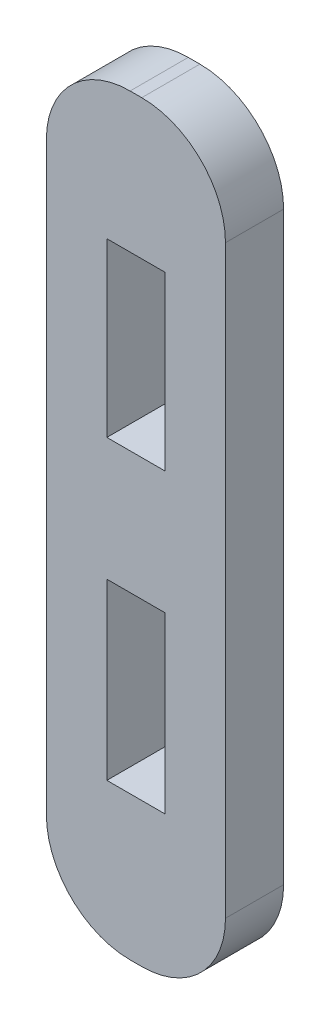
SolidWorks part; units mm, degrees
ref_plane "Front Plane" through (0, 0, 0) normal (0, 0, 1) x (1, 0, 0)
ref_plane "Top Plane" through (0, 0, 0) normal (0, 1, 0) x (1, 0, 0)
ref_plane "Right Plane" through (0, 0, 0) normal (1, 0, 0) x (0, 0, -1)
sketch "Sketch1" plane through (0, 0, 0) normal (0, 0, 1) x (1, 0, 0)
  line L0 (3.2385, 18.8942) -> (1.651, 18.8942) construction
  line L1 (0, 0) -> (4.8895, 0)
  line L2 (0, 0) -> (0, 20.5452)
  line L3 (0, 20.5452) -> (4.8895, 20.5452)
  line L4 (4.8895, 0) -> (4.8895, 20.5452)
  line L7 (3.2385, 16.7352) -> (3.2385, 18.8942) construction
  dimension "D1" = 1.651
  dimension "D2" = 1.651
extrude "Boss-Extrude1" add sketch "Sketch1" along normal blind 1.5875
sketch "Sketch2" plane through (0, 0, 0) normal (0, 0, -1) x (-1, 0, 0)
  line L1 (-3.2385, 14.1952) -> (-3.2385, 12.0362)
  line L2 (-3.2385, 12.0362) -> (-1.651, 12.0362)
  line L3 (-1.651, 12.0362) -> (-1.651, 14.1952)
  line L4 (-1.651, 15.6786) -> (-1.651, 18.5626) construction
  line L6 (-1.651, 16.7352) -> (-1.651, 18.8942) construction
  line L7 (-3.2385, 15.6786) -> (-3.2385, 18.5626) construction
  line L8 (-1.651, 5.2233) -> (-1.651, 6.4075) construction
  line L9 (-3.2385, 5.2233) -> (-3.2385, 4.8666) construction
  line L10 (-3.2385, 16.7352) -> (-1.651, 16.7352) construction
  line L11 (-3.2385, 6.4075) -> (-3.2385, 5.2233) construction
  line L12 (-1.651, 4.8666) -> (-1.651, 5.2233) construction
  line L13 (-1.651, 5.2233) -> (-1.651, 6.4075)
  line L14 (-1.651, 15.3513) -> (-1.651, 15.6786) construction
  line L15 (-1.651, 14.1952) -> (-1.651, 15.3513) construction
  line L16 (-3.2385, 16.7352) -> (-1.651, 16.7352)
  line L17 (-3.2385, 15.6786) -> (-3.2385, 15.3513) construction
  line L18 (-3.2385, 15.3513) -> (-3.2385, 14.1952) construction
  line L19 (-1.651, 15.6786) -> (-1.651, 16.7352)
  line L20 (-3.2385, 5.2233) -> (-3.2385, 4.8666)
  line L21 (-3.2385, 6.4075) -> (-3.2385, 5.2233)
  line L22 (-3.2385, 3.9278) -> (-1.651, 3.9278) construction
  line L25 (-3.2385, 15.6786) -> (-3.2385, 16.7352)
  line L26 (-1.651, 15.3513) -> (-1.651, 15.6786)
  line L27 (-1.651, 14.1952) -> (-1.651, 15.3513)
  line L28 (-3.2385, 15.6786) -> (-3.2385, 15.3513)
  line L29 (-3.2385, 3.9278) -> (-1.651, 3.9278)
  line L30 (-1.651, 4.8666) -> (-1.651, 5.2233)
  line L31 (-1.651, 1.9826) -> (-1.651, 4.8666) construction
  line L32 (-3.2385, 15.3513) -> (-3.2385, 14.1952)
  line L33 (-3.2385, 6.4075) -> (-3.2385, 8.6842)
  line L34 (-3.2385, 8.6842) -> (-1.651, 8.6842)
  line L35 (-1.651, 8.6842) -> (-1.651, 6.4075)
  line L36 (-1.651, 3.9278) -> (-1.651, 1.651) construction
  line L37 (-0.8554, 16.7352) -> (-0.8554, 18.8942) construction
  line L38 (-3.2385, 1.9826) -> (-3.2385, 4.8666) construction
  line L39 (-1.651, 3.9278) -> (-1.651, 4.8666)
  line L40 (-3.2385, 3.9278) -> (-3.2385, 4.8666)
  line L41 (-0.8554, 1.651) -> (-0.8554, 3.9278) construction
extrude "Cut-Extrude1" cut sketch "Sketch2" against normal through all
fillet "Fillet1" radius 2.286 4 edges at (0, 0, 0.7937) (4.8895, 0, 0.7937) (4.8895, 20.5452, 0.7937) (0, 20.5452, 0.7937)
